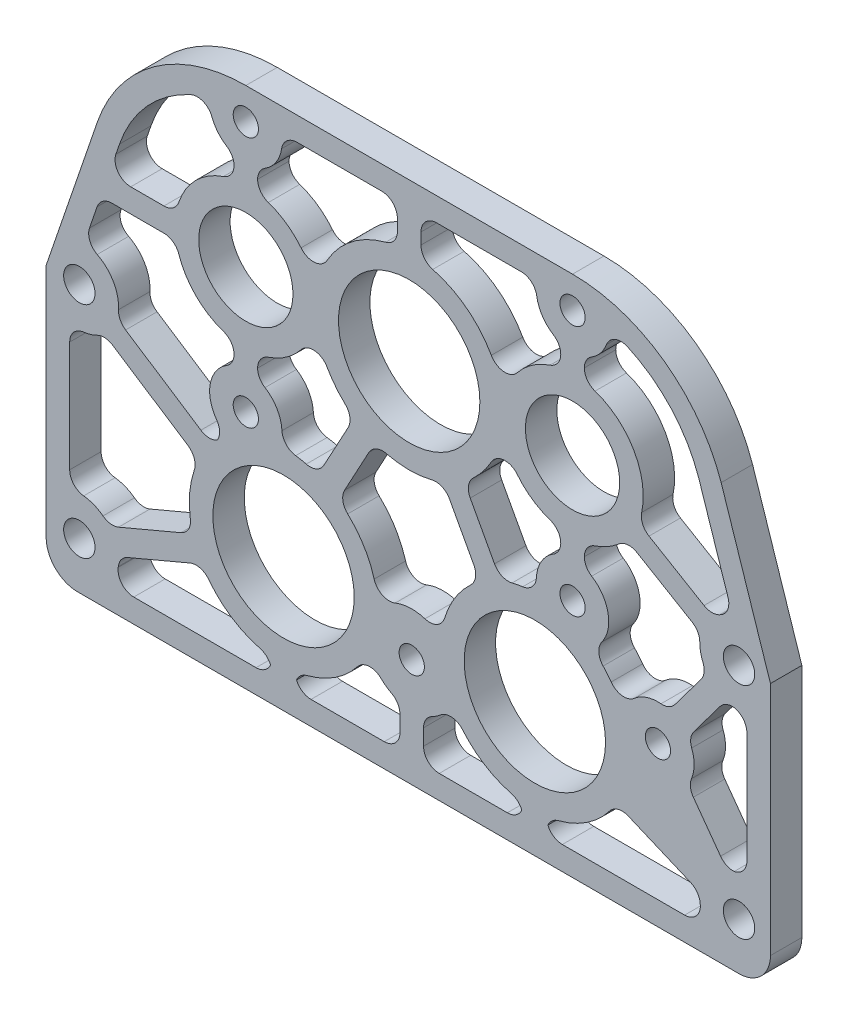
SolidWorks part; units mm, degrees
material "6061 Alloy"
ref_plane "Front Plane" through (0, 0, 0) normal (0, 0, 1) x (1, 0, 0)
ref_plane "Top Plane" through (0, 0, 0) normal (0, 1, 0) x (1, 0, 0)
ref_plane "Right Plane" through (0, 0, 0) normal (1, 0, 0) x (0, 0, -1)
sketch "Sketch1" plane through (0, 0, 0) normal (0, 0, 1) x (1, 0, 0)
  line L0 (0, 0) -> (-28088.6063, 0) construction
  line L1 (0, 0) -> (0, -28088.6063) construction
  line L2 (1.5394, 46.9041) -> (-37.2217, 46.9041) construction
  line L3 (50.8, 0) -> (50.8, 50000) construction
  line L4 (-7.62, 72.3041) -> (-7.62, 21.5041) construction
  line L5 (58.42, 72.3041) -> (58.42, 21.5041) construction
  line L6 (-110.2422, 36.5125) -> (49889.7578, 36.5125) construction
  line L7 (-115.6814, -26.9875) -> (-47.986, -26.9875) construction
  line L8 (25.9168, -5.0978) -> (75.6832, 5.0978) construction
  line L9 (-110.2422, 33.3375) -> (49889.7578, 33.3375) construction
  line L10 (-41.275, 26.9875) -> (92.075, 26.9875) construction
  line L11 (-41.275, 26.9875) -> (-41.275, -17.4625) construction
  line L12 (92.075, 26.9875) -> (92.075, -17.4625) construction
  line L13 (-41.275, -17.4625) -> (92.075, -17.4625) construction
  line L15 (-47.986, -26.9875) -> (98.425, -26.9875)
  line L16 (-37.662, 57.1775) -> (-47.986, 26.9875)
  line L17 (-47.986, 26.9875) -> (-47.986, -26.9875)
  line L18 (98.425, 26.9875) -> (98.425, -26.9875)
  line L20 (-7.62, 78.6541) -> (58.42, 78.6541)
  line L21 (98.425, 26.9875) -> (88.462, 57.1775)
  line L25 (-47.986, -26.9875) -> (98.425, -26.9875) construction
  circle A0 centre (0, 0) radius 14.2875
  circle A1 centre (50.8, 0) radius 14.2875
  circle A2 centre (25.4, 46.9041) radius 14.2875
  circle A3 centre (0, 0) radius 34.29 construction
  circle A4 centre (50.8, 0) radius 16.51 construction
  circle A5 centre (50.8, 0) radius 38.1 construction
  circle A6 centre (25.4, 46.9041) radius 25.4 construction
  circle A7 centre (-7.62, 46.9041) radius 7.62 construction
  circle A8 centre (58.42, 46.9041) radius 7.62 construction
  circle A9 centre (-7.62, 72.3041) radius 2.5527
  circle A10 centre (-7.62, 21.5041) radius 2.5527
  circle A11 centre (58.42, 72.3041) radius 2.5527
  circle A12 centre (58.42, 21.5041) radius 2.5527
  circle A13 centre (-7.62, 46.9041) radius 31.75 construction
  circle A14 centre (58.42, 46.9041) radius 31.75 construction
  circle A15 centre (58.42, 46.9041) radius 9.525
  circle A16 centre (-7.62, 46.9041) radius 9.525
  circle A17 centre (75.6832, 5.0978) radius 2.5527
  circle A18 centre (25.9168, -5.0978) radius 2.5527
  circle A19 centre (-41.275, 26.9875) radius 3.175
  circle A20 centre (92.075, 26.9875) radius 3.175
  circle A21 centre (-41.275, -17.4625) radius 3.175
  circle A22 centre (92.075, -17.4625) radius 3.175
  circle A23 centre (92.075, 26.9875) radius 6.35 construction
  circle A24 centre (50.8, 0) radius 39.37 construction
  circle A25 centre (-41.275, 26.9875) radius 6.35 construction
  circle A26 centre (-41.275, -17.4625) radius 6.35 construction
  circle A27 centre (92.075, -17.4625) radius 6.35 construction
  arc A28 (58.42, 78.6541) -> (88.462, 57.1775) centre (58.42, 46.9041) cw
  arc A29 (-37.662, 57.1775) -> (-7.62, 78.6541) centre (-7.62, 46.9041) cw
  circle A30 centre (25.4, 46.9041) radius 15.24 construction
  dimension "D1" = 28.575
  dimension "D2" = 68.58
  dimension "D3" = 33.02
  dimension "D4" = 76.2
  dimension "D5" = 50.8
  dimension "D6" = 15.24
  dimension "D10" = 5.1054
  dimension "D11" = 63.5
  dimension "D12" = 19.05
  dimension "D16" = 5.1054
  dimension "D18" = 6.35
  dimension "D25" = 12.7
  dimension "D26" = 78.74
  dimension "D27" = 30.48
  dimension "D7" = 25.4
  dimension "D8" = 50.8
  dimension "D9" = 25.4
  dimension "D13" = 36.5125
  dimension "D14" = 26.9875
  dimension "D15" = 50.8
  dimension "D17" = 5.0978
  dimension "D21" = 41.275
  dimension "D22" = 6.35
  dimension "D20" = 41.275
  dimension "D23" = 9.525
  dimension "D19" = 3.175
extrude "Boss-Extrude2" add sketch "Sketch1" along normal blind 6.35
fillet "Fillet1" radius 6.35 2 edges at (98.425, -26.9875, 3.175) (-47.986, -26.9875, 3.175)
sketch "Sketch3" plane through (0, 0, 6.35) normal (0, 0, 1) x (1, 0, 0)
  line L0 (-7.62, 72.3041) -> (-7.62, 46.9041) construction
  line L1 (-7.62, 46.9041) -> (-7.62, 21.5041) construction
  line L2 (-7.62, 21.5041) -> (0, 0) construction
  line L3 (0, 0) -> (25.9168, -5.0978) construction
  line L4 (25.9168, -5.0978) -> (50.8, 0) construction
  line L5 (50.8, 0) -> (58.42, 21.5041) construction
  line L6 (58.42, 21.5041) -> (58.42, 46.9041) construction
  line L7 (58.42, 46.9041) -> (58.42, 72.3041) construction
  line L8 (0, 0) -> (25.4, 46.9041) construction
  line L9 (25.4, 46.9041) -> (50.8, 0) construction
  line L10 (25.4, 46.9041) -> (25.4, 73.8916) construction
  line L11 (58.42, 46.9041) -> (92.075, 26.9875) construction
  line L12 (92.075, 26.9875) -> (75.6832, 5.0978) construction
  line L13 (75.6832, 5.0978) -> (92.075, -17.4625) construction
  line L14 (25.9168, -5.0978) -> (25.9168, -22.225) construction
  line L15 (-41.275, 26.9875) -> (0, 0) construction
  line L16 (0, 0) -> (-41.275, -17.4625) construction
  line L17 (50.8, 0) -> (92.075, -17.4625) construction
  line L18 (23.5356, -5.0978) -> (23.5356, -22.225)
  line L19 (28.2981, -5.0978) -> (28.2981, -22.225)
  line L20 (-0.9278, 2.1931) -> (-42.2028, -15.2694)
  line L21 (-42.5781, 24.9945) -> (-1.3031, -1.993)
  line L22 (2.0939, -1.1339) -> (27.4939, 45.7702)
  line L23 (23.3061, 45.7702) -> (48.7061, -1.1339)
  line L24 (27.7812, 46.9041) -> (27.7812, 73.8916)
  line L25 (60.8013, 21.5041) -> (60.8013, 46.9041)
  line L26 (-10.0013, 72.3041) -> (-10.0013, 46.9041)
  line L27 (-10.0013, 46.9041) -> (-10.0013, 21.5041)
  line L28 (60.8013, 46.9041) -> (60.8012, 72.3041)
  line L29 (57.2073, 44.8548) -> (90.8623, 24.9382)
  line L30 (0.9278, -2.1931) -> (-40.3472, -19.6556)
  line L31 (-39.9719, 28.9805) -> (1.3031, 1.993)
  line L32 (-2.0939, 1.1339) -> (23.3061, 48.038)
  line L33 (27.4939, 48.038) -> (52.8939, 1.1339)
  line L34 (23.0187, 46.9041) -> (23.0187, 73.8916)
  line L35 (56.0388, 21.5041) -> (56.0388, 46.9041)
  line L36 (-5.2388, 72.3041) -> (-5.2388, 46.9041)
  line L37 (-5.2388, 46.9041) -> (-5.2388, 21.5041)
  line L38 (56.0388, 46.9041) -> (56.0387, 72.3041)
  line L39 (59.6327, 48.9534) -> (93.2877, 29.0368)
  line L40 (90.1689, 28.4148) -> (72.7242, 5.1191)
  line L41 (-43.2235, 26.1957) -> (-43.2235, -20.6375)
  line L42 (-41.636, -22.225) -> (92.075, -22.225)
  line L43 (93.6625, -20.6375) -> (93.6625, 26.222)
  line L44 (93.6625, 26.222) -> (83.9477, 55.6598)
  line L45 (58.42, 73.8916) -> (-7.62, 73.8916)
  line L46 (-33.1557, 55.6365) -> (-43.2235, 26.1957)
  line L47 (-43.2235, 26.1957) -> (-43.2235, -20.6375)
  line L48 (-41.636, -22.225) -> (92.075, -22.225)
  line L49 (93.6625, -20.6375) -> (93.6625, 26.222)
  line L50 (93.6625, 26.222) -> (83.9477, 55.6598)
  line L51 (58.42, 73.8916) -> (-7.62, 73.8916)
  line L52 (-33.1557, 55.6365) -> (-43.2235, 26.1957)
  line L53 (72.7242, 5.1191) -> (85.1127, -11.9313)
  line L54 (51.7278, 2.1931) -> (85.1127, -11.9313)
  line L55 (93.9811, 25.5602) -> (78.6421, 5.0765)
  line L56 (78.6421, 5.0765) -> (99.0373, -22.9937)
  line L57 (49.8722, -2.1931) -> (99.0373, -22.9937)
  line L58 (-7.62, 46.9041) -> (-36.1419, 46.9041) construction
  line L59 (-7.62, 49.2854) -> (-36.1419, 49.2854)
  line L60 (-7.62, 44.5229) -> (-39.3651, 44.5229)
  line L61 (-7.62, 44.5229) -> (-36.1419, 44.5229) construction
  circle A2 centre (-7.62, 72.3041) radius 7.3152
  circle A3 centre (-7.62, 72.3041) radius 7.3152
  circle A4 centre (58.42, 72.3041) radius 7.3152
  circle A5 centre (58.42, 72.3041) radius 7.3152
  circle A7 centre (-41.275, 26.9875) radius 7.9375
  circle A8 centre (-41.275, 26.9875) radius 7.9375
  circle A10 centre (-41.275, -17.4625) radius 7.9375
  circle A11 centre (-41.275, -17.4625) radius 7.9375
  circle A13 centre (92.075, -17.4625) radius 7.9375
  circle A14 centre (92.075, -17.4625) radius 7.9375
  circle A16 centre (92.075, 26.9875) radius 7.9375
  circle A17 centre (92.075, 26.9875) radius 7.9375
  circle A19 centre (-7.62, 46.9041) radius 14.2875
  circle A20 centre (-7.62, 46.9041) radius 14.2875
  circle A22 centre (25.4, 46.9041) radius 19.05
  circle A23 centre (25.4, 46.9041) radius 19.05
  circle A25 centre (58.42, 46.9041) radius 14.2875
  circle A26 centre (58.42, 46.9041) radius 14.2875
  arc A28 (-43.2235, -20.6375) -> (-41.636, -22.225) centre (-41.636, -20.6375) ccw
  arc A29 (92.075, -22.225) -> (93.6625, -20.6375) centre (92.075, -20.6375) ccw
  arc A30 (83.9477, 55.6598) -> (58.42, 73.8916) centre (58.42, 46.9041) ccw
  arc A31 (-7.62, 73.8916) -> (-33.1557, 55.6365) centre (-7.62, 46.9041) ccw
  arc A32 (-43.2235, -20.6375) -> (-41.636, -22.225) centre (-41.636, -20.6375) ccw
  arc A33 (92.075, -22.225) -> (93.6625, -20.6375) centre (92.075, -20.6375) ccw
  arc A34 (83.9477, 55.6598) -> (58.42, 73.8916) centre (58.42, 46.9041) ccw
  arc A35 (-7.62, 73.8916) -> (-33.1557, 55.6365) centre (-7.62, 46.9041) ccw
  circle A36 centre (58.42, 21.5041) radius 7.3152
  circle A37 centre (58.42, 21.5041) radius 7.3152
  circle A39 centre (-7.62, 21.5041) radius 7.3152
  circle A40 centre (-7.62, 21.5041) radius 7.3152
  circle A42 centre (0, 0) radius 19.05
  circle A43 centre (0, 0) radius 19.05
  circle A45 centre (25.9168, -5.0978) radius 8.9027
  circle A46 centre (25.9168, -5.0978) radius 8.9027
  circle A48 centre (50.8, 0) radius 19.05
  circle A49 centre (50.8, 0) radius 19.05
  circle A51 centre (75.6832, 5.0978) radius 7.3152
  circle A52 centre (75.6832, 5.0978) radius 7.3152
  dimension "D1" = 4.7625
  dimension "D2" = 4.7625
  dimension "D3" = 4.7625
  dimension "D4" = 4.7625
  dimension "D5" = 4.7625
  dimension "D6" = 4.7625
  dimension "D7" = 4.7625
  dimension "D8" = 4.7625
  dimension "D9" = 4.7625
  dimension "D10" = 4.7625
  dimension "D11" = 4.7625
  dimension "D12" = 4.7625
  dimension "D13" = 4.7625
  dimension "D14" = 6.35
  dimension "D15" = 4.7625
  dimension "D16" = 4.7625
  dimension "D17" = 2.3813
  dimension "D18" = 2.3813
  dimension "D19" = 2.3813
  dimension "D20" = 2.3813
  dimension "D21" = 2.3813
  dimension "D22" = 2.3813
  dimension "D23" = 2.3813
  dimension "D24" = 2.3813
extrude "Cut-Extrude3" cut sketch "Sketch3" against normal blind 10.795 contours A43 A40 L27 A20 L60 L52 A8 L31 | A3 A35 L52 L59 A20 L26 | A43 L21 A8 L47 A11 L20 | A46 A43 L30 A11 L48 L18 | A49 A46 L19 L48 A14 L57 | A49 L23 A23 L22 A43 A46 | A43 L32 A23 A20 L37 A40 | A23 L34 L51 A3 L36 A20 | A26 L38 A5 L51 L24 A23 | A49 A37 L35 A26 A23 L33 | L50 A34 A5 L28 A26 L39 A17 | A52 L40 A17 L29 A26 L25 A37 A49 | A52 L56 A14 L49 A17 L55 region at (22.9333, -17.9506, 6.35) region at (32.0285, -12.3607, 6.35) region at (25.3759, 16.111, 6.35) region at (-32.1637, 3.739, 6.35) region at (4.5834, 29.1568, 6.35) region at (88.8658, 4.8418, 6.35) region at (-24.4909, 30.9179, 6.35) region at (46.2166, 29.1568, 6.35) region at (-22.6058, 59.9928, 6.35) region at (8.446, 65.9004, 6.35) region at (72.7069, 23.498, 6.35) region at (42.354, 65.9004, 6.35) region at (76.5021, 53.1952, 6.35)
fillet "Fillet3" radius 3.175 81 edges at (56.0388, 28.4209, 3.175) (56.0388, 32.8164, 3.175) (44.3141, 44.6331, 3.175) (36.4942, 31.418, 3.175) (43.8937, 17.754, 3.175) (51.5338, 19.0359, 3.175) (-14.9119, 72.8878, 3.175) (-10.0013, 65.3873, 3.175) (-10.0013, 60.9918, 3.175) (-21.7077, 49.2854, 3.175) (-35.3276, 49.2854, 3.175) (-40.2606, 34.8599, 3.175) (-36.9562, 44.5229, 3.175) (-21.7077, 44.5229, 3.175) (-10.0013, 32.8164, 3.175) (-10.0013, 28.4209, 3.175) (-11.4157, 15.2507, 3.175) (-14.5161, 12.3364, 3.175) (-33.6344, 24.8368, 3.175) (-43.2235, 19.2929, 3.175) (-36.2407, 20.8508, 3.175) (-18.3347, -5.1714, 3.175) (-17.1224, 8.3503, 3.175) (-33.3737, -16.7052, 3.175) (-43.2235, -9.7679, 3.175) (-35.2294, -12.3191, 3.175) (-34.925, -22.225, 3.175) (-16.479, -9.5575, 3.175) (17.4118, -7.7287, 3.175) (23.5356, -13.6761, 3.175) (23.5356, -22.225, 3.175) (28.2981, -22.225, 3.175) (28.2981, -13.6761, 3.175) (33.9621, -8.9099, 3.175) (67.279, -9.5575, 3.175) (84.1737, -16.7052, 3.175) (85.725, -22.225, 3.175) (93.6625, -9.6854, 3.175) (89.5506, -9.9371, 3.175) (81.7352, 9.207, 3.175) (81.6753, 0.9018, 3.175) (89.4424, 19.4993, 3.175) (93.6625, 19.2104, 3.175) (84.3459, 28.7945, 3.175) (85.6303, 22.3539, 3.175) (77.9231, 12.0616, 3.175) (68.5789, 6.8419, 3.175) (62.2157, 15.2507, 3.175) (60.8013, 28.4209, 3.175) (60.8013, 32.8164, 3.175) (69.331, 37.6801, 3.175) (86.7714, 32.8931, 3.175) (90.8232, 34.8257, 3.175) (71.7565, 41.7787, 3.175) (65.7119, 72.8878, 3.175) (60.8013, 60.9918, 3.175) (60.8013, 65.3873, 3.175) (51.2791, 73.8916, 3.175) (56.0388, 65.3873, 3.175) (56.0388, 60.9918, 3.175) (44.3141, 49.1751, 3.175) (27.7812, 65.8047, 3.175) (27.7812, 73.8916, 3.175) (23.0187, 65.8047, 3.175) (23.0187, 73.8916, 3.175) (-0.4791, 73.8916, 3.175) (-5.2388, 65.3873, 3.175) (-5.2388, 60.9918, 3.175) (6.4859, 49.1751, 3.175) (39.7058, 15.4862, 3.175) (31.8149, 1.5709, 3.175) (19.0418, 0.5584, 3.175) (11.0942, 15.4862, 3.175) (32.3063, 29.1501, 3.175) (18.4937, 29.1501, 3.175) (6.9063, 17.754, 3.175) (-0.7338, 19.0359, 3.175) (14.3058, 31.418, 3.175) (-5.2388, 28.4209, 3.175) (-5.2388, 32.8164, 3.175) (6.4859, 44.6331, 3.175)
sketch "Sketch4" plane through (0, 0, 6.35) normal (0, 0, 1) x (1, 0, 0)
  line L0 (0, -19.05) -> (0, -26.9875) construction
  line L1 (-41.636, -26.9875) -> (92.075, -26.9875) construction
  line L2 (50.8, -19.05) -> (50.8, -26.9875) construction
  line L3 (-2.3813, -18.9006) -> (-2.3812, -26.9875)
  line L4 (48.4188, -18.9006) -> (48.4188, -26.9875)
  line L5 (2.3813, -18.9006) -> (2.3813, -26.9875)
  line L6 (53.1813, -18.9006) -> (53.1813, -26.9875)
  line L7 (2.3813, 0) -> (2.3813, -26.9875) construction
  line L8 (0, 0) -> (0, -26.9875) construction
  line L9 (-2.3813, 0) -> (-2.3812, -26.9875) construction
  line L10 (53.1813, 0) -> (53.1813, -26.9875) construction
  line L11 (50.8, 0) -> (50.8, -26.9875) construction
  line L12 (48.4188, 0) -> (48.4188, -26.9875) construction
  line L13 (-2.3812, -26.9875) -> (2.3813, -26.9875)
  line L14 (48.4188, -26.9875) -> (53.1813, -26.9875)
  arc A0 (-2.3813, -18.9006) -> (2.3813, -18.9006) centre (0, 0) ccw
  arc A1 (48.4188, -18.9006) -> (53.1813, -18.9006) centre (50.8, 0) ccw
  dimension "D1" = 2.3813
  dimension "D2" = 2.3813
extrude "Boss-Extrude3" add sketch "Sketch4" against normal through all
fillet "Fillet4" radius 3.175 8 edges at (53.1813, -18.9006, 3.175) (53.1813, -22.225, 3.175) (48.4188, -22.225, 3.175) (48.4188, -18.9006, 3.175) (-2.3813, -18.9006, 3.175) (-2.3813, -22.225, 3.175) (2.3813, -22.225, 3.175) (2.3812, -18.9006, 3.175)
equation "\"D2@Sketch1\"=54/20"
equation "\"D3@Sketch1\"=26/20"
equation "\"D4@Sketch1\"=60/20"
equation "\"D5@Sketch1\"=40/20"
equation "\"D6@Sketch1\"=12/20"
equation "\"D9@Sketch1\"=\"D8@Sketch1\"/2"
equation "\"D20@Sketch1\"=\"D21@Sketch1\""
